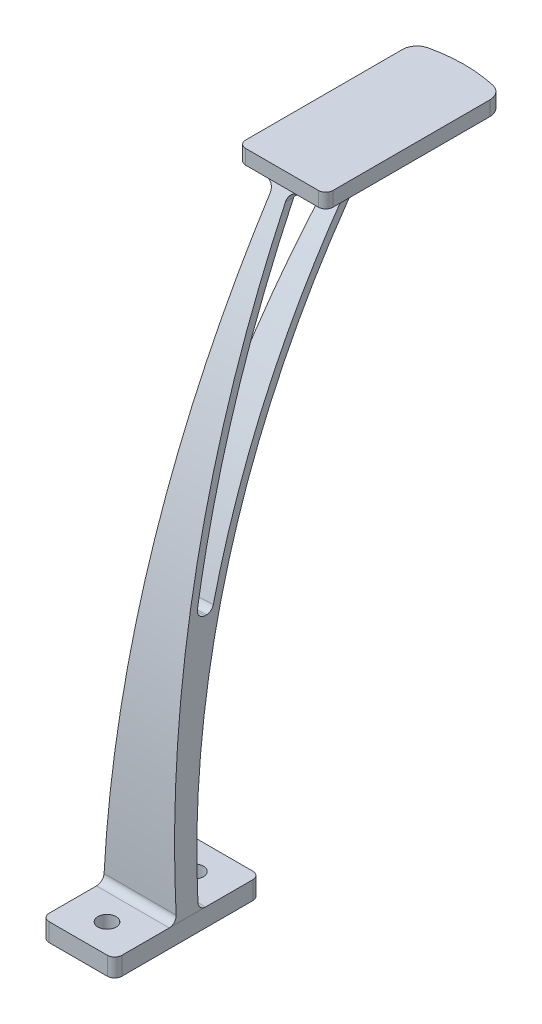
SolidWorks part; units mm, degrees
ref_plane "前视基准面" through (0, 0, 0) normal (0, 0, 1) x (1, 0, 0)
ref_plane "上视基准面" through (0, 0, 0) normal (0, 1, 0) x (1, 0, 0)
ref_plane "右视基准面" through (0, 0, 0) normal (1, 0, 0) x (0, 0, -1)
other "Configuration Table"
sketch "草图1" plane through (0, 0, 0) normal (1, 0, 0) x (0, 0, -1)
  line L1 (0, 0) -> (53, 0)
  line L2 (0, 0) -> (0, -80)
  line L3 (0, -80) -> (53, -80)
  line L4 (53, 0) -> (53, -80)
  dimension "D1" = 80
  dimension "D2" = 53
extrude "凸台-拉伸1" add sketch "草图1" along normal blind 12
sketch "草图2" plane through (12, 0, 0) normal (1, 0, 0) x (0, 0, -1)
  line L0 (10, -77.5) -> (10, -76.5)
  line L1 (0, -80) -> (20, -80)
  line L2 (0, -80) -> (0, -77.5)
  line L3 (0, -77.5) -> (20, -77.5)
  line L4 (20, -80) -> (20, -77.5)
  line L5 (53, 0) -> (28, 0)
  line L6 (53, 0) -> (53, -2)
  line L7 (53, -2) -> (28, -2)
  line L8 (28, 0) -> (28, -2)
  line L9 (28, -2) -> (40, -2)
  line L10 (11.5, -77.5) -> (8.5, -77.5)
  line L11 (11.5, -77.5) -> (11.5, -76.5)
  line L12 (11.5, -76.5) -> (8.5, -76.5)
  line L13 (8.5, -77.5) -> (8.5, -76.5)
  line L14 (11.5, -77.5) -> (8.5, -76.5) construction
  line L15 (11.5, -76.5) -> (8.5, -77.5) construction
  arc A0 (8.5, -76.5) -> (28, -2) centre (160.5641, -76.5) cw
  arc A1 (11.5, -76.5) -> (40, -2) centre (123.1228, -76.5) cw
  point P12 (10, -77)
  line M13 (0, 0) -> (0, -80)
  line M14 (0, -80) -> (53, -80)
  line M15 (53, -80) -> (53, 0)
  line M16 (53, 0) -> (0, 0)
  dimension "D1" = 2
  dimension "D2" = 2.5
  dimension "D3" = 20
  dimension "D4" = 25
  dimension "D5" = 3
  dimension "D6" = 1
  dimension "D7" = 12
extrude "切除-拉伸1" cut sketch "草图2" against normal blind 12 contours L13 A0 L8 L3 M16 M13 | A1 L11 L3 L4 L7 M14 M15
sketch "草图3" plane through (0, -80, 0) normal (0, -1, 0) x (1, 0, 0)
  line L0 (6, 0) -> (6, -20)
  line L1 (12, 0) -> (0, 0) construction
  line L2 (0, -20) -> (12, -20) construction
  line L4 (11, -53.425) -> (1, -53.425)
  line L5 (11, -53.425) -> (11, 0)
  line L6 (11, 0) -> (1, 0)
  line L7 (1, -53.425) -> (1, 0)
  line L8 (11, -53.425) -> (1, 0) construction
  line L9 (11, 0) -> (1, -53.425) construction
  line L10 (12, -53) -> (0, -53)
  line L11 (12, -53) -> (12, 0)
  line L12 (12, 0) -> (0, 0)
  line L13 (0, -53) -> (0, 0)
  point P6 (6, -26.7125)
  line M6 (0, -20) -> (12, -20)
  line M7 (12, -20) -> (12, 0)
  line M8 (12, 0) -> (0, 0)
  line M9 (0, 0) -> (0, -20)
  dimension "D1" = 10
extrude "切除-拉伸2" cut sketch "草图3" against normal up to surface (78 mm away) contours L10 L11 L5 M6 | L13 L10 L7 M6 | L5 M6 M7 M8 | L7 M6 M8 M9 up to face at (6, -2, -46.5)
sketch "草图4" plane through (0, 0, 0) normal (0, 0, 1) x (1, 0, 0)
  line L0 (5, -2) -> (1, -77.5)
  line L1 (1, -2) -> (11, -2) construction
  line L2 (1, -77.5) -> (1, -2)
  line L3 (1, -2) -> (5, -2)
  line L4 (6, -2) -> (6, -77.5)
  line L5 (1, -77.5) -> (11, -77.5) construction
  line L6 (11, -77.5) -> (11, -2)
  line L7 (7, -2) -> (11, -77.5)
  line L8 (11, -2) -> (7, -2)
  dimension "D1" = 2
extrude "切除-拉伸3" cut sketch "草图4" against normal blind 200 contours L3 L2 L0 | L6 L8 L7
sketch "草图5" plane through (6.8747, 0.3642, 0) normal (0.9986, 0.0529, 0) x (0, 0, -1)
  line L8 (12.9181, -44.9734) -> (15.1282, -44.9734)
  line L9 (20, -77.9734) -> (11.5, -77.9734) construction
  line L12 (9.5, -76.9734) -> (10.5, -76.9734)
  line L13 (10.5, -76.9734) -> (10.5, -76.972)
  line L14 (37.7922, -3.3675) -> (28.5868, -3.3675)
  line L15 (9.5, -76.972) -> (9.5, -76.9734)
  line L16 (9.5, -76.9734) -> (10.5, -76.9734)
  line L17 (10.5, -76.9734) -> (10.5, -76.972)
  line L18 (37.7922, -3.3675) -> (28.5868, -3.3675)
  line L19 (9.5, -76.972) -> (9.5, -76.9734)
  spline S0 degree 3 poles (3732.4819, -1458.9655) (751.5554, -695.2556) (-32.354, -305.6032) (12.8655, -53.7392) (13.5985, -50.4875) (14.9185, -45.6474) (15.3952, -44.0403) (16.4235, -40.8389) (16.9767, -39.2405) (19.9057, -31.3531) (22.7734, -25.3461) (149.7236, 189.9523) (949.2527, 9.0925) (3776.5092, -1343.0227) knots -9.234133 -9.234133 -9.234133 -9.234133 0.25 0.25 0.375 0.375 0.4375 0.4375 0.5 0.5 0.75 0.75 9.915725 9.915725 9.915725 9.915725 only from (10.5, -76.972) to (37.7922, -3.3675)
  spline S1 degree 3 poles (3958.4428, -508.2882) (977.9739, 241.9547) (125.5932, 242.2736) (17.9785, -26.6008) (15.9907, -32.6432) (13.5795, -41.9078) (12.8711, -45.0297) (11.9547, -49.7639) (11.6734, -51.3528) (11.1622, -54.5348) (10.9323, -56.1279) (-32.2578, -393.2788) (1050.336, -824.8056) (3740.2164, -1393.3761) knots -10.874836 -10.874836 -10.874836 -10.874836 0.25 0.25 0.5 0.5 0.625 0.625 0.6875 0.6875 0.75 0.75 13.895765 13.895765 13.895765 13.895765 only from (28.5868, -3.3675) to (9.5, -76.972)
  spline S2 degree 3 poles (10.5, -76.972) (10.5, -70.219) (11.1008, -63.5683) (12.8655, -53.7392) (13.5985, -50.4875) (14.9185, -45.6474) (15.3952, -44.0403) (16.4235, -40.8389) (16.9767, -39.2405) (19.9057, -31.3531) (22.7734, -25.3461) (29.5148, -13.9132) (33.3884, -8.4872) (37.7922, -3.3675) knots 0 0 0 0 0.25 0.25 0.375 0.375 0.4375 0.4375 0.5 0.5 0.75 0.75 1 1 1 1
  spline S3 degree 3 poles (28.5868, -3.3675) (25.4513, -9.0055) (22.7088, -14.782) (17.9785, -26.6008) (15.9907, -32.6432) (13.5795, -41.9078) (12.8711, -45.0297) (11.9547, -49.7639) (11.6734, -51.3528) (11.1622, -54.5348) (10.9323, -56.1279) (9.9104, -64.1047) (9.5, -70.5209) (9.5, -76.972) knots 0 0 0 0 0.25 0.25 0.5 0.5 0.625 0.625 0.6875 0.6875 0.75 0.75 1 1 1 1
  dimension "D2" = 33
  dimension "D1" = 1
extrude "切除-拉伸4" cut sketch "草图5" against normal blind 200 contours L18 S3 L8 S2
fillet "圆角1" radius 1 2 edges
fillet "圆角2" radius 2 1 edges at (6, -2, -40)
sketch "草图6" plane through (0, 0, 0) normal (0, 1, 0) x (1, 0, 0)
  line L0 (12, 53) -> (0, 53) construction
  line L5 (0, 28) -> (12, 28)
  line L6 (12, 28) -> (12, 53)
  line L7 (12, 53) -> (0, 53)
  line L8 (0, 53) -> (0, 28)
  line L9 (0, 28) -> (12, 28)
  line L10 (12, 28) -> (12, 53)
  line L11 (12, 53) -> (0, 53)
  line L12 (0, 53) -> (0, 28)
  circle A0 centre (6.0252, 33) radius 20
  line M8 (12, 53) -> (0, 53)
  line M9 (0, 53) -> (0, 28)
  dimension "D1" = 40
  dimension "D2" = 0
extrude "切除-拉伸5" cut sketch "草图6" against normal blind 200 contours A0 L11 M9 | A0 L10 M8
fillet "圆角3" radius 2 2 edges at (12, -1, -52.0867) (0, -1, -52.0708)
fillet "圆角4" radius 1 2 edges at (5, -2, -34.449) (7, -2, -34.449)
sketch "草图7" plane through (0, -80, 0) normal (0, -1, 0) x (1, 0, 0)
  line L0 (6, -15.9545) -> (6, -3.9545)
  line L1 (1, -10) -> (11, -10)
  line L2 (1, -20) -> (1, 0) construction
  line L3 (11, -20) -> (11, 0) construction
  circle A0 centre (6, -3.9545) radius 1.25
  circle A1 centre (6, -15.9545) radius 1.25
  point P3 (6, -9.9545)
  dimension "D2" = 2.5
  dimension "D3" = 2.5
  dimension "D1" = 12
extrude "切除-拉伸6" cut sketch "草图7" against normal blind 5
fillet "圆角5" radius 1 4 edges at (11, -78.75, 0) (11, -78.75, -20) (1, -78.75, 0) (1, -78.75, -20)
fillet "圆角6" radius 1 2 edges at (6, -77.5, -8.5) (6, -77.5, -11.5)
fillet "圆角7" radius 1 2 edges at (0, -1, -28) (12, -1, -28)
